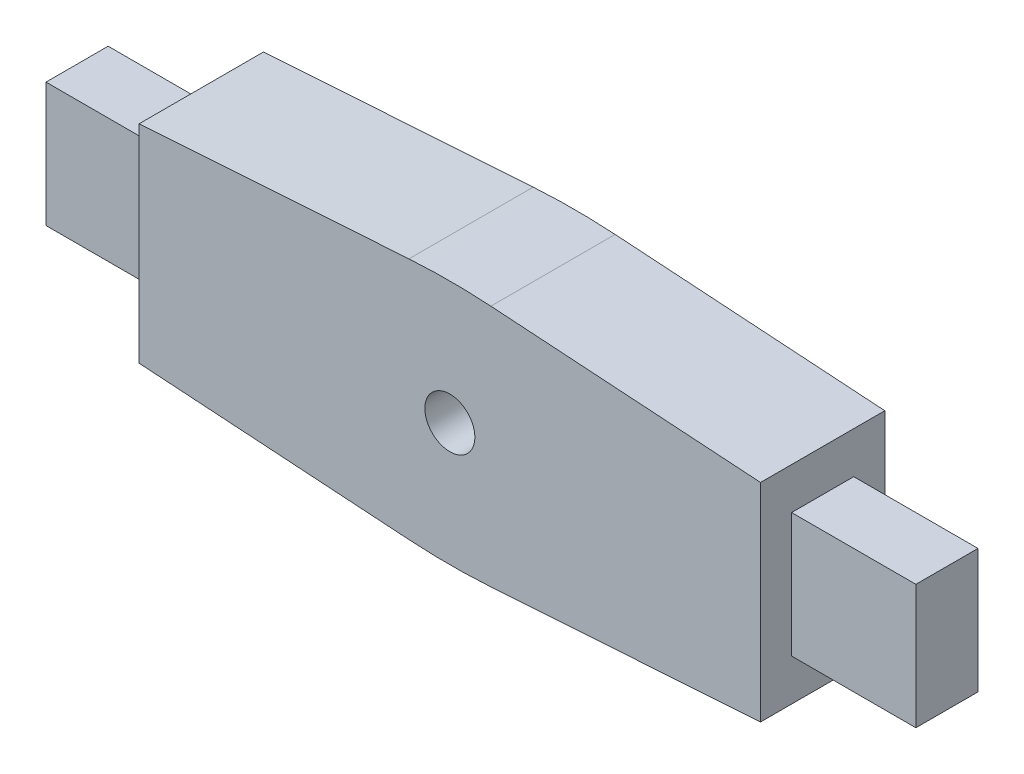
SolidWorks part; units mm, degrees
ref_plane "Front Plane" through (0, 0, 0) normal (0, 0, 1) x (1, 0, 0)
ref_plane "Top Plane" through (0, 0, 0) normal (0, 1, 0) x (1, 0, 0)
ref_plane "Right Plane" through (0, 0, 0) normal (1, 0, 0) x (0, 0, -1)
sketch "Sketch1" plane through (0, 0, 0) normal (0, 0, 1) x (1, 0, 0)
  line L0 (0, 0) -> (-50000, 0) construction
  line L1 (0, -20) -> (151.3167, -10) construction
  line L2 (0, 20) -> (151.3167, 10) construction
  line L3 (0, 0) -> (0, 50000) construction
  line L4 (122.4484, -204.4828) -> (119.5098, 130.5043) construction
  line L5 (0, -20) -> (-151.3167, -10) construction
  line L6 (0, 20) -> (-151.3167, 10) construction
  line L7 (50, 16.6957) -> (50, -16.6957)
  line L8 (50, 16.6957) -> (0, 20)
  line L9 (0, -20) -> (50, -16.6957)
  line L10 (0, -20) -> (-50, -16.6957)
  line L11 (-50, 16.6957) -> (-50, -16.6957)
  line L12 (-50, 16.6957) -> (0, 20)
  circle A1 centre (0, 0) radius 4.025
  arc A2 (-151.3167, -10) -> (-151.3167, 10) centre (-150.6558, 0) ccw construction
  arc A3 (151.3167, -10) -> (151.3167, 10) centre (150.6558, 0) cw construction
  dimension "D1" = 40
  dimension "D2" = 8.05
  dimension "D3" = 20
  dimension "D4" = 30
  dimension "D5" = 50
extrude "Boss-Extrude1" add sketch "Sketch1" along normal blind 20
fillet "Fillet1" radius 100 2 edges at (0, 20, 10) (0, -20, 10)
sketch "Sketch2" plane through (50, 0, 0) normal (1, 0, 0) x (0, 0, -1)
  line L1 (-15, 10) -> (-5, 10)
  line L2 (-15, 10) -> (-15, -10)
  line L3 (-15, -10) -> (-5, -10)
  line L4 (0, -16.6957) -> (0, 16.6957)
  line L5 (-20, -16.6957) -> (0, -16.6957)
  line L6 (-20, 16.6957) -> (-20, -16.6957)
  line L7 (0, 16.6957) -> (-20, 16.6957)
  line L8 (0, -16.6957) -> (0, 16.6957)
  line L9 (-20, -16.6957) -> (0, -16.6957)
  line L10 (-20, 16.6957) -> (-20, -16.6957)
  line L11 (0, 16.6957) -> (-20, 16.6957)
  line L12 (-5, 10) -> (-5, -10)
  line L13 (-15, 10) -> (-5, -10) construction
  line L14 (-15, -10) -> (-5, 10) construction
  point P2 (-10, 0)
  point P10 (-10, -16.6957)
  dimension "D2" = 10
  dimension "D3" = 20
  dimension "D1" = 0
extrude "Boss-Extrude2" add sketch "Sketch2" along normal blind 20 contours L12 L1 L2 L3 region at (50, 0, 10)
mirror "Mirror1" about plane through (0, 0, 0) normal (1, 0, 0) of "Boss-Extrude2"
